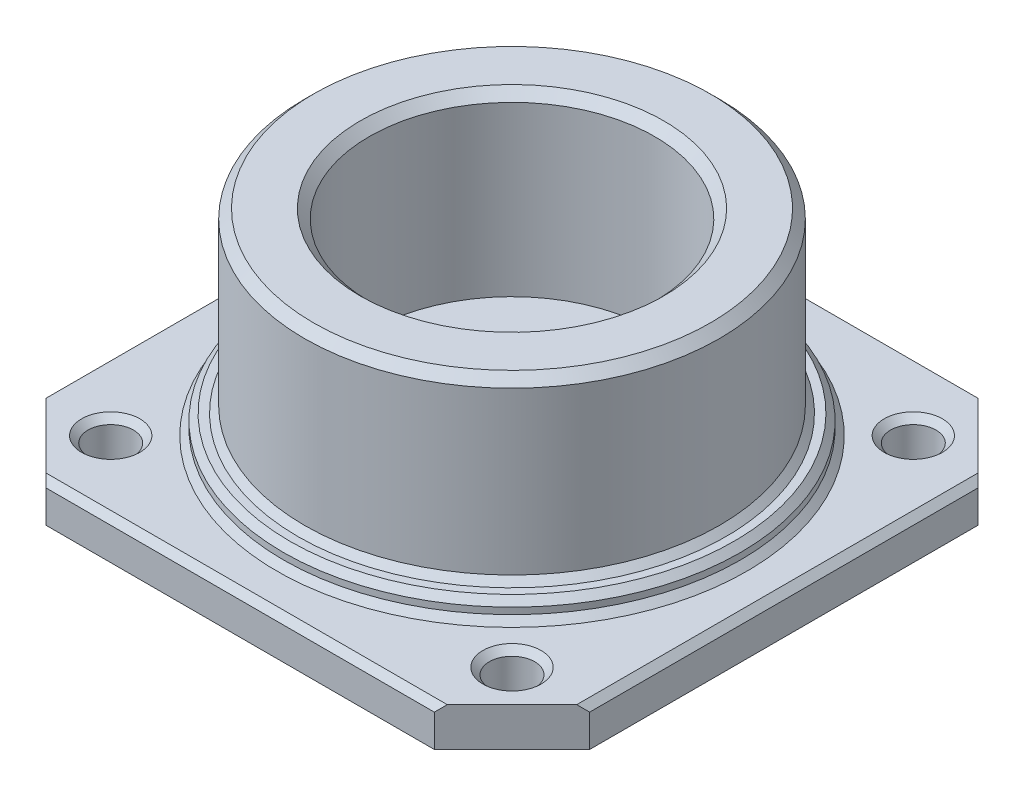
SolidWorks part; units mm, degrees
ref_plane "前视基准面" through (0, 0, 0) normal (0, 0, 1) x (1, 0, 0)
ref_plane "上视基准面" through (0, 0, 0) normal (0, 1, 0) x (1, 0, 0)
ref_plane "右视基准面" through (0, 0, 0) normal (1, 0, 0) x (0, 0, -1)
other "Configuration Table"
sketch "草图1" plane through (0, 0, 0) normal (0, 1, 0) x (1, 0, 0)
  line L1 (-21, -21) -> (21, -21)
  line L2 (-21, -21) -> (-21, 21)
  line L3 (-21, 21) -> (21, 21)
  line L4 (21, -21) -> (21, 21)
  line L5 (-21, -21) -> (21, 21) construction
  line L6 (-21, 21) -> (21, -21) construction
  circle A0 centre (0, 0) radius 12.65
  circle A1 centre (-15.5, 15.5) radius 1.75
  circle A2 centre (15.5, 15.5) radius 1.75
  circle A3 centre (15.5, -15.5) radius 1.75
  circle A4 centre (-15.5, -15.5) radius 1.75
  point P0 (0, 0)
  dimension "D3" = 25.3
  dimension "D4" = 3.5
  dimension "D1" = 42
  dimension "D2" = 42
  dimension "D5" = 31
extrude "凸台-拉伸1" add sketch "草图1" along normal blind 2
sketch "草图2" plane through (0, 2, 0) normal (0, 1, 0) x (1, 0, 0)
  circle A0 centre (0, 0) radius 12.65 construction
  circle A1 centre (0, 0) radius 12.65
  circle A2 centre (0, 0) radius 17.65
  dimension "D1" = 5
extrude "凸台-拉伸2" add sketch "草图2" along normal blind 0.1
sketch "草图3" plane through (0, 2.1, 0) normal (0, 1, 0) x (1, 0, 0)
  circle A0 centre (0, 0) radius 11.025
  circle A1 centre (0, 0) radius 3.95
  circle A2 centre (0, 0) radius 17.65 construction
  circle A3 centre (0, 0) radius 17.65
  circle M1 centre (0, 0) radius 17.65
  circle M2 centre (0, 0) radius 12.65
  dimension "D1" = 22.05
  dimension "D2" = 7.9
extrude "凸台-拉伸3" add sketch "草图3" along normal blind 1.4 contours M1 M2 | A0 M2 | A0 A1
sketch "草图4" plane through (0, 3.5, 0) normal (0, 1, 0) x (1, 0, 0)
  circle A0 centre (0, 0) radius 16.025
  circle A3 centre (0, 0) radius 3.95
  circle A4 centre (0, 0) radius 3.95
  circle A5 centre (0, 0) radius 11.025
  circle A6 centre (0, 0) radius 11.025
  dimension "D4" = 22.05
  dimension "D1" = 5
  dimension "D2" = 0
  dimension "D3" = 0
extrude "凸台-拉伸4" add sketch "草图4" along normal blind 14 contours A0 A6
chamfer "倒角2" distance 0.5 angle 45 13 edges at (15.5, 2, 17.25) (0, 2.1, 3.95) (0, 3.5, 3.95) (-15.5, 2, 17.25) (-15.5, 2, -13.75) (15.5, 2, -13.75) (0, 3.5, 17.65) (0, 3.5, 16.025) (-21, 2, 0) (0, 2, -21) (21, 2, 0) (0, 2, 21) (0, 2, 17.65)
chamfer "倒角3" distance 1 angle 45 2 edges at (0, 17.5, 16.025) (0, 17.5, 11.025)
chamfer "倒角4" distance 6 angle 45 4 edges at (-21, 0.75, -21) (-21, 0.75, 21) (21, 0.75, 21) (21, 0.75, -21)
sketch "草图5" plane through (0, 17.5, 0) normal (0, 1, 0) x (1, 0, 0)
  line L1 (-30.8533, 26.6247) -> (47.6634, 26.6247)
  line L2 (-30.8533, 26.6247) -> (-30.8533, -29.8614)
  line L3 (-30.8533, -29.8614) -> (47.6634, -29.8614)
  line L4 (47.6634, 26.6247) -> (47.6634, -29.8614)
extrude "切除-拉伸1" cut sketch "草图5" against normal blind 0.3
sketch "草图7" plane through (0, 0, 0) normal (0, -1, 0) x (1, 0, 0)
  line L8 (-21, 15) -> (-21, -15)
  line L9 (-21, -15) -> (-15, -21)
  line L10 (-15, -21) -> (15, -21)
  line L11 (15, -21) -> (21, -15)
  line L12 (21, -15) -> (21, 15)
  line L13 (21, 15) -> (15, 21)
  line L14 (15, 21) -> (-15, 21)
  line L15 (-15, 21) -> (-21, 15)
  line L16 (-21, 15) -> (-21, -15)
  line L17 (-21, -15) -> (-15, -21)
  line L18 (-15, -21) -> (15, -21)
  line L19 (15, -21) -> (21, -15)
  line L20 (21, -15) -> (21, 15)
  line L21 (21, 15) -> (15, 21)
  line L22 (15, 21) -> (-15, 21)
  line L23 (-15, 21) -> (-21, 15)
  circle A0 centre (0, 0) radius 12.65 construction
  circle A1 centre (15.5, 15.5) radius 1.75
  circle A2 centre (15.5, 15.5) radius 1.75
  circle A3 centre (-15.5, 15.5) radius 1.75
  circle A4 centre (-15.5, 15.5) radius 1.75
  circle A5 centre (0, 0) radius 12.65
  circle A6 centre (-15.5, -15.5) radius 1.75 construction
  circle A7 centre (15.5, -15.5) radius 1.75 construction
  circle A8 centre (15.5, -15.5) radius 1.75
  circle A9 centre (-15.5, -15.5) radius 1.75
  dimension "D1" = 0
  dimension "D2" = 0
  dimension "D3" = 0
extrude "凸台-拉伸5" add sketch "草图7" along normal blind 1
